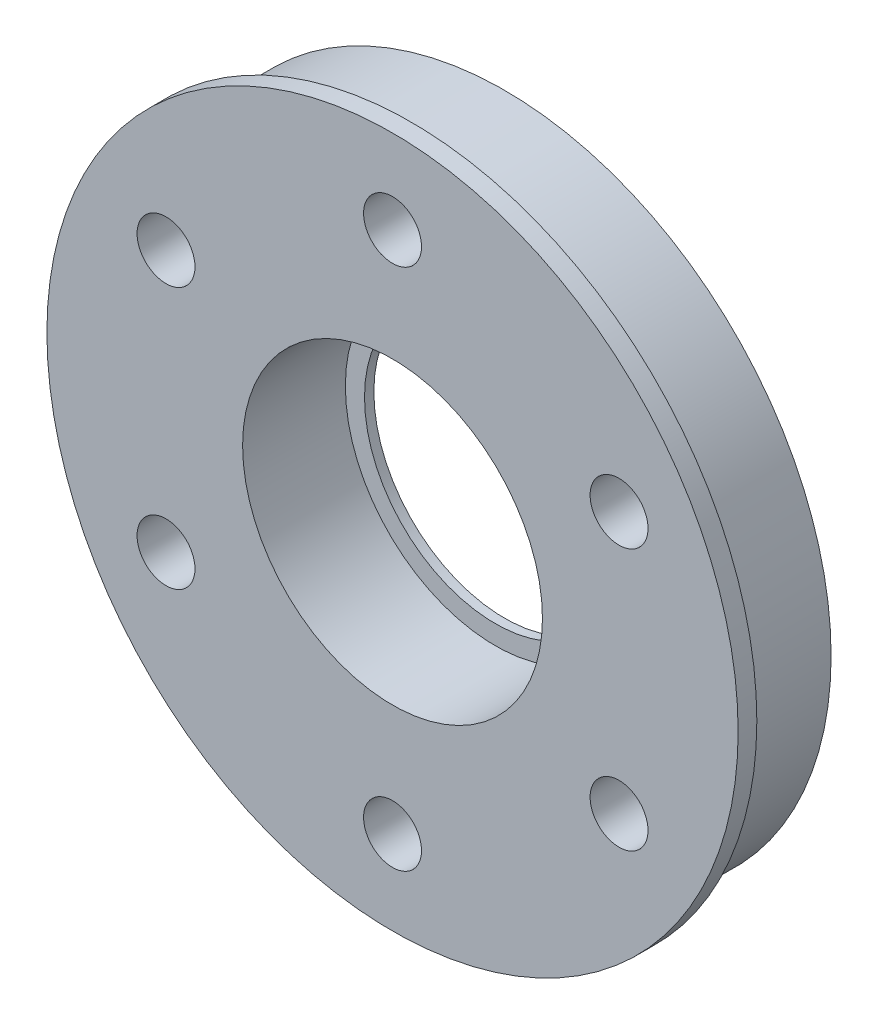
SolidWorks part; units mm, degrees
ref_plane "Front Plane" through (0, 0, 0) normal (0, 0, 1) x (1, 0, 0)
ref_plane "Top Plane" through (0, 0, 0) normal (0, 1, 0) x (1, 0, 0)
ref_plane "Right Plane" through (0, 0, 0) normal (1, 0, 0) x (0, 0, -1)
sketch "Sketch1" plane through (0, 0, 0) normal (0, 0, 1) x (1, 0, 0)
  line L0 (0, 0) -> (0, 28.3945) construction
  circle A0 centre (0, 0) radius 8.025
  circle A1 centre (0, 0) radius 17.475
  circle A2 centre (0, 14) radius 1.55
  circle A3 centre (12.1244, 7) radius 1.55
  circle A4 centre (12.1244, -7) radius 1.55
  circle A5 centre (0, -14) radius 1.55
  circle A6 centre (-12.1244, -7) radius 1.55
  circle A7 centre (-12.1244, 7) radius 1.55
  point P22 (0, 0)
  dimension "D1" = 34.95
  dimension "D2" = 16.05
  dimension "D3" = 3.1
  dimension "D4" = 14
  dimension "D5" = 6
extrude "Boss-Extrude1" add sketch "Sketch1" along normal blind 6 contours A7 | A6 | A5 | A4 | A3 | L0 A2 | A2 L0 | A0 A2 A1 A7 A6 A5 A4 A3 region at (12.0072, 12.0072, 0) region at (-0.6578, 14, 0) region at (0.6578, 14, 0) region at (12.1244, 7, 0) region at (12.1244, -7, 0) region at (0, -14, 0) region at (-12.1244, -7, 0) region at (-12.1244, 7, 0)
extrude "Cut-Extrude1" cut sketch "Sketch1<3>" against normal blind 4 from surface contours A7 | A2 L0 | L0 A2 | A3 | A4 | A5 | A6 region at (-0.6578, 14, 0) region at (0.6578, 14, 0) region at (12.1244, 7, 0) region at (12.1244, -7, 0) region at (0, -14, 0) region at (-12.1244, -7, 0) region at (-12.1244, 7, 0) starting at face at (17.475, 0, 6)
sketch "Sketch1<3>" plane through (0, 0, 0) normal (0, 0, 1) x (1, 0, 0) same geometry as "Sketch1"
sketch "Sketch2" plane through (0, 0, 0) normal (0, 0, 1) x (1, 0, 0)
  circle A0 centre (0, 0) radius 18.5
  circle A1 centre (0, 0) radius 17.25
  circle A2 centre (0, 0) radius 8.25
  circle A3 centre (0, 0) radius 7
  dimension "D1" = 34.5
  dimension "D2" = 37
  dimension "D3" = 16.5
  dimension "D4" = 14
extrude "Boss-Extrude2" add sketch "Sketch2" against normal blind 1 from surface contours A0 A1 region at (-17.9767, 0, 0) starting at face at (-10.5744, -7, 6)
extrude "Boss-Extrude3" add sketch "Sketch2<3>" along normal blind 0.5 from surface contours A2 A3 region at (-8.0167, 0, 0) starting at face at (17.475, 0, 0)
sketch "Sketch2<3>" plane through (0, 0, 0) normal (0, 0, 1) x (1, 0, 0) same geometry as "Sketch2"
